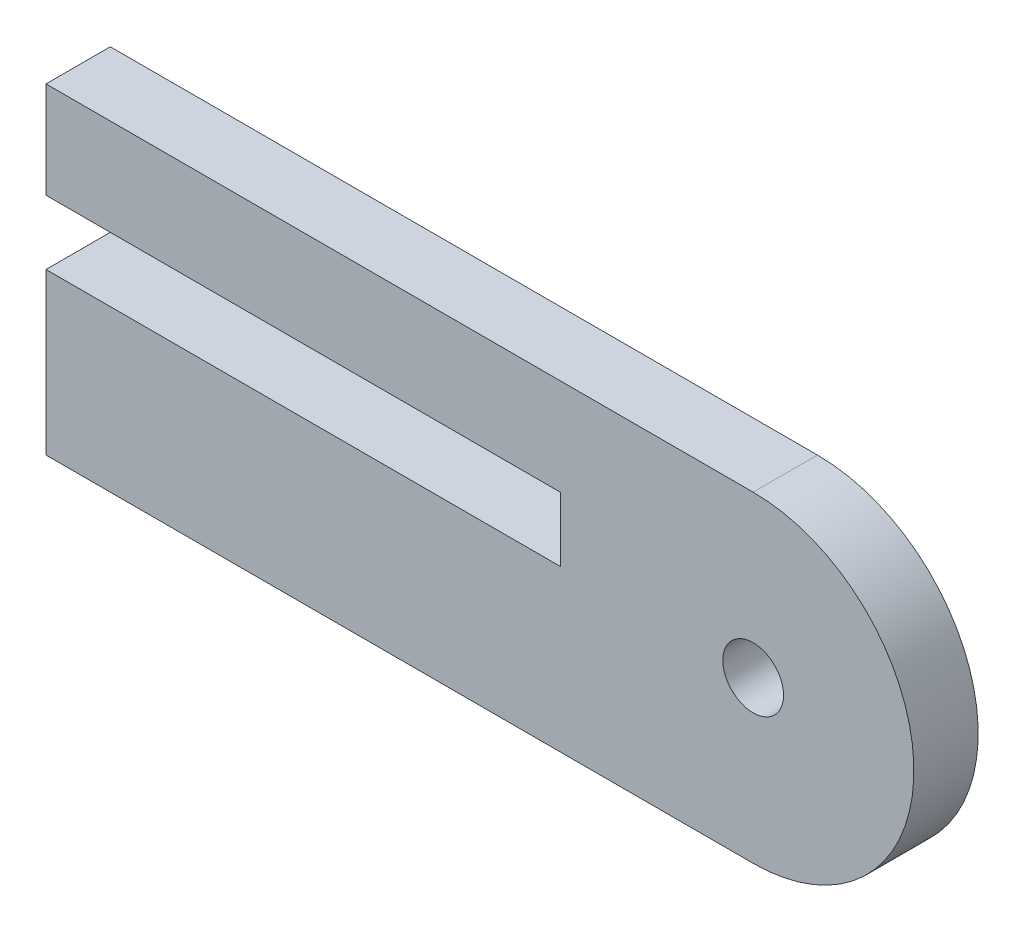
SolidWorks part; units mm, degrees
ref_plane "Front Plane" through (0, 0, 0) normal (0, 0, 1) x (1, 0, 0)
ref_plane "Top Plane" through (0, 0, 0) normal (0, 1, 0) x (1, 0, 0)
ref_plane "Right Plane" through (0, 0, 0) normal (1, 0, 0) x (0, 0, -1)
sketch "Sketch1" plane through (0, 0, 0) normal (0, 0, 1) x (1, 0, 0)
  line L0 (26.9875, 7.9375) -> (42.8625, 7.9375) construction
  line L1 (0, 0) -> (34.925, 0)
  line L2 (0, 0) -> (0, 4.7625)
  line L3 (0, 15.875) -> (34.925, 15.875)
  line L4 (42.8625, 0) -> (42.8625, 7.9375) construction
  line L5 (0, 11.1125) -> (25.4, 11.1125)
  line L6 (0, 11.1125) -> (0, 4.7625) construction
  line L7 (0, 4.7625) -> (26.9875, 4.7625) construction
  line L8 (26.9875, 11.1125) -> (26.9875, 4.7625) construction
  line L9 (42.8625, 7.9375) -> (42.8625, 15.875) construction
  line L10 (34.925, 0) -> (42.8625, 0) construction
  line L11 (34.925, 15.875) -> (42.8625, 15.875) construction
  line L12 (0, 4.7625) -> (0, 11.1125) construction
  line L13 (0, 11.1125) -> (0, 15.875)
  line L14 (25.4, 11.1125) -> (25.4, 7.9375)
  line L15 (0, 4.7625) -> (26.9875, 4.7625) construction
  line L16 (0, 4.7625) -> (0, 7.9375)
  line L17 (0, 7.9375) -> (25.4, 7.9375)
  line L18 (26.9875, 4.7625) -> (26.9875, 7.9375)
  line L19 (25.4, 11.1125) -> (26.9875, 11.1125) construction
  line L20 (25.4, 7.9375) -> (26.9875, 7.9375) construction
  arc A0 (34.925, 0) -> (34.925, 15.875) centre (34.925, 7.9375) ccw
  arc A1 (26.9875, 7.9375) -> (34.925, 0) centre (34.925, 7.9375) ccw construction
  arc A2 (34.925, 15.875) -> (26.9875, 7.9375) centre (34.925, 7.9375) ccw construction
  circle A3 centre (34.925, 7.9375) radius 1.5
  point P15 (34.925, 7.9375)
  dimension "D5" = 15.875
  dimension "D6" = 3
  dimension "D1" = 15.875
  dimension "D2" = 6.35
  dimension "D3" = 26.9875
  dimension "D4" = 15.875
  dimension "D7" = 25.4
extrude "Boss-Extrude1" add sketch "Sketch1" along normal blind 3.175 contours L1 A0 L3 L13 L5 L8 L7 L2 A3 | L17 L16 L7 L8 region at (21.5677, 7.7112, 0)
